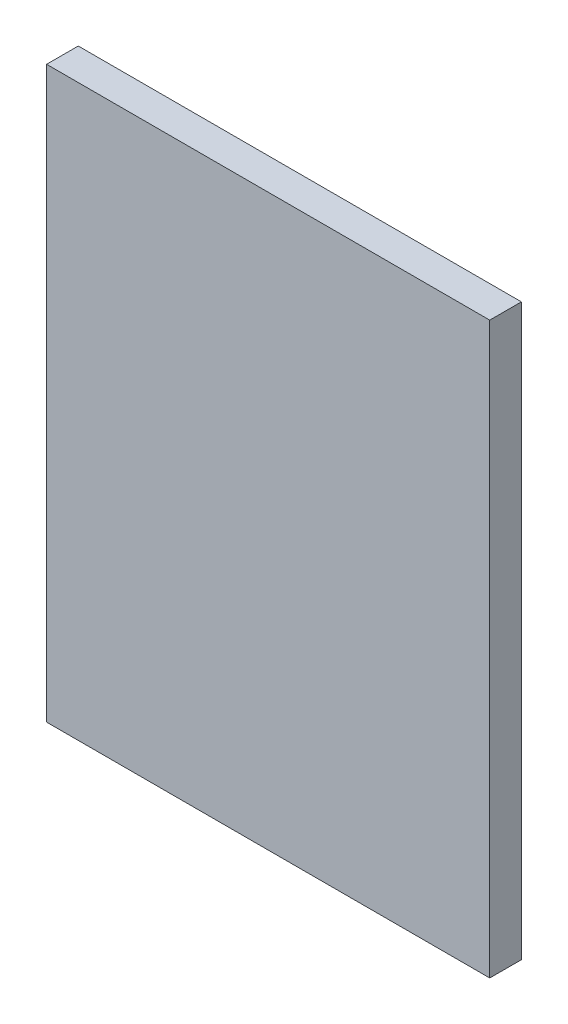
SolidWorks part; units mm, degrees
ref_plane "Front Plane" through (0, 0, 0) normal (0, 0, 1) x (1, 0, 0)
ref_plane "Top Plane" through (0, 0, 0) normal (0, 1, 0) x (1, 0, 0)
ref_plane "Right Plane" through (0, 0, 0) normal (1, 0, 0) x (0, 0, -1)
sketch "Sketch1" plane through (0, 0, 0) normal (0, 0, 1) x (1, 0, 0)
  line L1 (-35, -45) -> (35, -45)
  line L2 (-35, -45) -> (-35, 45)
  line L3 (-35, 45) -> (35, 45)
  line L4 (35, -45) -> (35, 45)
  line L5 (-35, -45) -> (35, 45) construction
  line L6 (-35, 45) -> (35, -45) construction
  point P0 (0, 0)
  dimension "D1" = 70
  dimension "D2" = 90
extrude "Boss-Extrude1" add sketch "Sketch1" along normal mid plane 5
